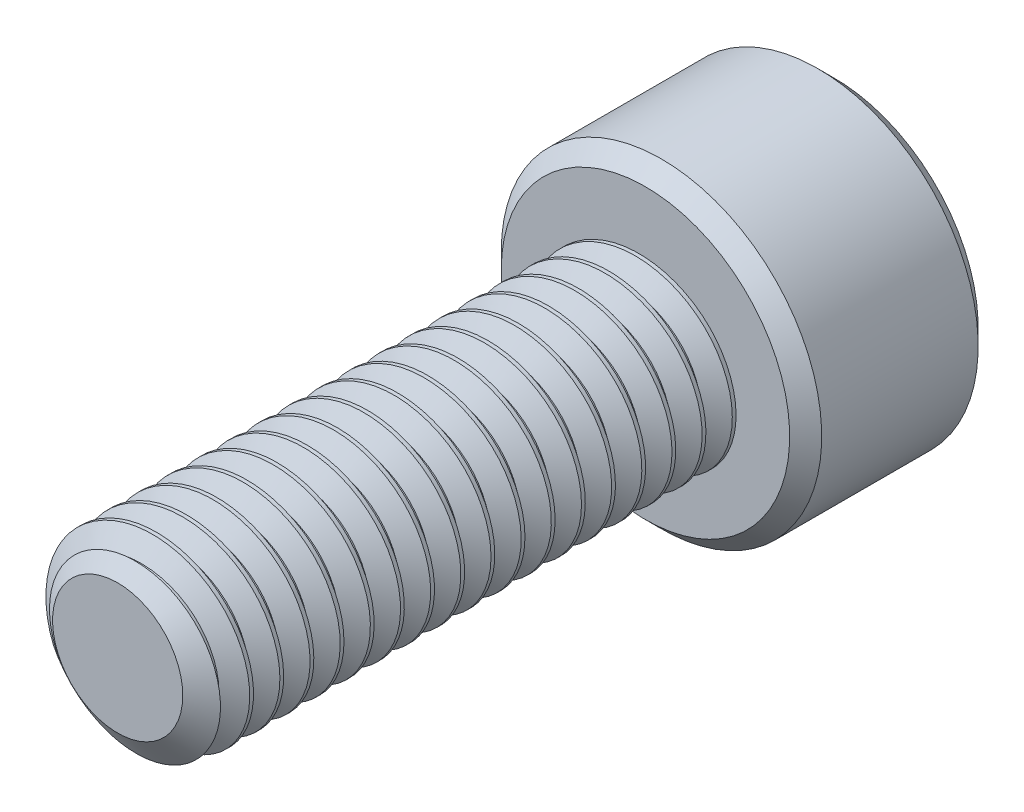
SolidWorks part; units mm, degrees
other "DetailItem1"
ref_plane "Front Plane" through (0, 0, 0) normal (0, 0, 1) x (1, 0, 0)
ref_plane "Top Plane" through (0, 0, 0) normal (0, 1, 0) x (1, 0, 0)
ref_plane "Right Plane" through (0, 0, 0) normal (1, 0, 0) x (0, 0, -1)
sketch "Sketch1" plane through (0, 0, 0) normal (0, 0, 1) x (1, 0, 0)
  circle A0 centre (0, 0) radius 2.5
  dimension "OD" = 5
extrude "Extrude1" add sketch "Sketch1" against normal blind 14
sketch "Sketch2" plane through (0, 0, 0) normal (0, 0, 1) x (1, 0, 0)
  circle A0 centre (0, 0) radius 2.5 construction
  circle A1 centre (0, 0) radius 2.5
curve "Helix/Spiral1" pitch 0.8 height 14.8 turns 18.5 parameters "pitch"=0.8
sketch "Sketch3" plane through (0, 0, 0) normal (1, 0, 0) x (0, 0, -1)
  line L0 (-0.7, 2.5) -> (-0.4, 1.9804)
  line L1 (-0.4, 1.9804) -> (-0.3, 1.9804)
  line L2 (-0.3, 1.9804) -> (0, 2.5)
  line L3 (-0.7, 2.5) -> (0, 2.5)
  line L4 (-0.35, 2.5) -> (-0.35, 1.9804) construction
  line L5 (-0.55, 2.2402) -> (-0.15, 2.2402) construction
  line L6 (0, 2.5) -> (0, -2.5) construction
  dimension "D1" = 0.1
  dimension "D2" = 0.4
  dimension "D3" = 60
sweep "Cut-Sweep1" cut profiles "Sketch3" path "Helix/Spiral1"
sketch "Sketch4" plane through (0, 0, 0) normal (1, 0, 0) x (0, 0, -1)
  line L0 (0.5417, 2.5) -> (0, 1.7264)
  line L1 (0, 1.7264) -> (0, 2.5)
  line L2 (0.5417, 2.5) -> (0, 2.5)
  line L3 (-0.7, 2.5) -> (0, 2.5) construction
  line L4 (0, 0) -> (7.0209, 0) construction
  dimension "D1" = 55
  dimension "D2" = 0.254
revolve "Cut-Revolve1" cut sketch "Sketch4" angle 360 about L4
sketch "Sketch6" plane through (0, 0, -14) normal (0, 0, -1) x (-1, 0, 0)
  circle A0 centre (0, 0) radius 4.25
  dimension "head dia" = 8.5
extrude "Extrude2" add sketch "Sketch6" along normal blind 5
sketch "Sketch7" plane through (0, 0, -19) normal (0, 0, -1) x (-1, 0, 0)
  line L1 (0, 2.3094) -> (-2, 1.1547)
  line L2 (-2, 1.1547) -> (-2, -1.1547)
  line L3 (-2, -1.1547) -> (0, -2.3094)
  line L4 (0, -2.3094) -> (2, -1.1547)
  line L5 (2, -1.1547) -> (2, 1.1547)
  line L6 (2, 1.1547) -> (0, 2.3094)
  circle A0 centre (0, 0) radius 2 construction
  dimension "hex dia" = 4
extrude "Cut-Extrude1" cut sketch "Sketch7" against normal blind 3
sketch "Sketch8" plane through (0, 0, -19) normal (0, 0, -1) x (-1, 0, 0)
  circle A0 centre (0, 0) radius 2.3094
extrude "Cut-Extrude2" cut sketch "Sketch8" against normal through all draft 45
chamfer "Chamfer1" distance 0.425 angle 45 2 edges at (-4.25, 0, -19) (-4.25, 0, -14)
sketch "Sketch10" plane through (0, 0, -14) normal (0, 0, 1) x (1, 0, 0)
  circle A1 centre (0, 0) radius 2.5
  circle A2 centre (0, 0) radius 2.5
  dimension "D1" = 0
ref_plane "Plane1" through (0, 0, 0) normal (0, 0, 1) x (1, 0, 0)
extrude "partial thread" [suppressed] add sketch "Sketch10" along normal up to surface (13 mm away) separate body
chamfer "Chamfer2" [suppressed] distance 0.1 angle 45
combine bodies "Combine1" [suppressed] operation type add bodies to combine 107 108
sketch "Sketch9" plane through (0, 0, 0) normal (1, 0, 0) x (0, 0, -1)
  line L0 (0, 2.5) -> (0, -2.5) construction
  line L1 (2, 2.5) -> (2, -2.5) construction
  dimension "D1" = 2
equation "\"D3@Helix/Spiral1\" = \"screw length@Extrude1\"+\"pitch@Helix/Spiral1\""
equation "\"D1@Sketch3\" = \"pitch@Helix/Spiral1\"*.125"
equation "\"D2@Sketch3\" = \"pitch@Helix/Spiral1\"*.5"
equation "\"D1@Cut-Extrude1\" = \"hex dia@Sketch7\"*.75"
equation "\"D1@Chamfer1\" = \"head dia@Sketch6\"*.05"
equation "\"D1@Sketch9\" = \"pitch@Helix/Spiral1\"*2.5"
equation "\"D1@Chamfer2\"=\"OD@Sketch1\"*.02"
